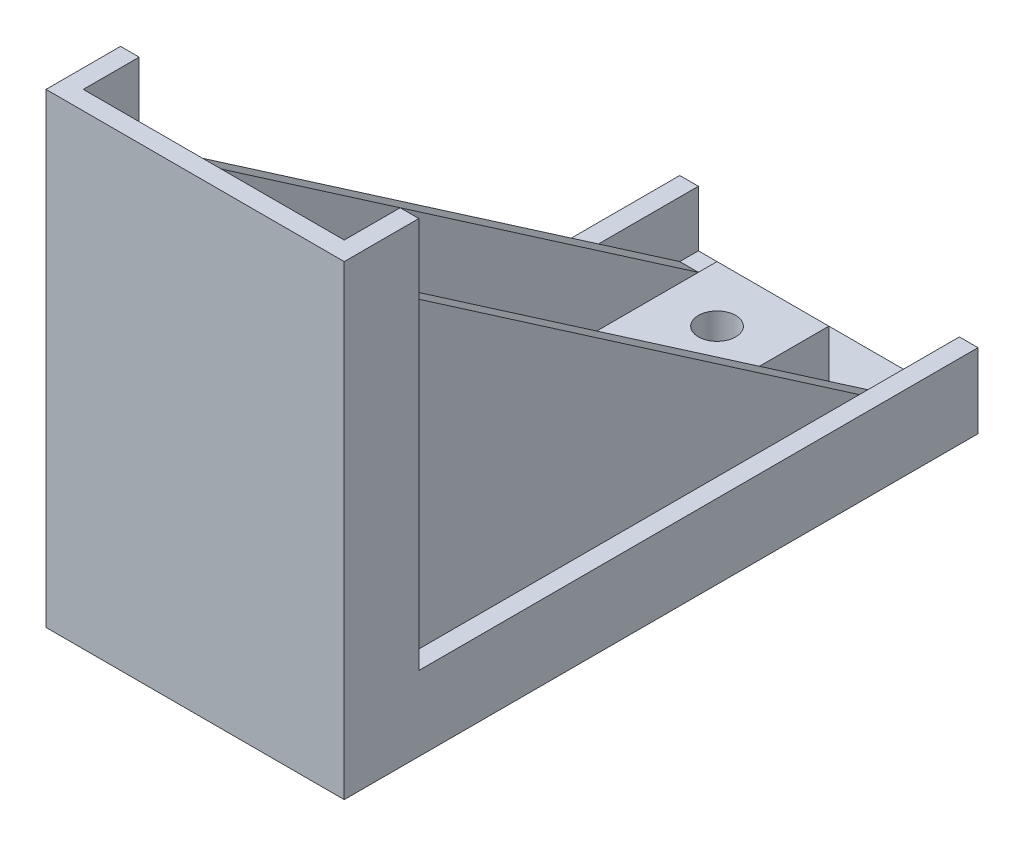
SolidWorks part; units mm, degrees
material "Plain Carbon Steel"
ref_plane "Front Plane" through (0, 0, 0) normal (0, 0, 1) x (1, 0, 0)
ref_plane "Top Plane" through (0, 0, 0) normal (0, 1, 0) x (1, 0, 0)
ref_plane "Right Plane" through (0, 0, 0) normal (1, 0, 0) x (0, 0, -1)
sketch "Sketch1" plane through (0, 0, 0) normal (0, 1, 0) x (1, 0, 0)
  line L0 (-10, 0) -> (10, 0)
  line L1 (10, 0) -> (10, 5)
  line L2 (10, 5) -> (8.75, 5)
  line L3 (8.75, 5) -> (8.75, 1.25)
  line L4 (8.75, 1.25) -> (-8.75, 1.25)
  line L5 (-8.75, 1.25) -> (-8.75, 5)
  line L6 (-8.75, 5) -> (-10, 5)
  line L7 (-10, 5) -> (-10, 0)
  dimension "D1" = 1.25
  dimension "D2" = 1.25
  dimension "D3" = 5
  dimension "D4" = 20
  dimension "D5" = 10
extrude "Boss-Extrude1" add sketch "Sketch1" along normal blind 31.25
sketch "Sketch2" plane through (0, 0, -1.25) normal (0, 0, -1) x (-1, 0, 0)
  line L0 (-10, 5) -> (-10, 0)
  line L1 (-10, 31.25) -> (-10, 0) construction
  line L2 (-10, 0) -> (10, 0)
  line L3 (10, 0) -> (10, 5)
  line L4 (10, 31.25) -> (10, 0) construction
  line L5 (10, 5) -> (8.75, 5)
  line L6 (8.75, 31.25) -> (8.75, 0) construction
  line L7 (8.75, 5) -> (8.75, 1.25)
  line L8 (8.75, 31.25) -> (8.75, 0) construction
  line L9 (8.75, 1.25) -> (-8.75, 1.25)
  line L10 (-8.75, 31.25) -> (-8.75, 0) construction
  line L11 (-8.75, 1.25) -> (-8.75, 5)
  line L12 (-8.75, 5) -> (-10, 5)
  dimension "D1" = 5
  dimension "D2" = 1.25
extrude "Boss-Extrude2" add sketch "Sketch2" along normal blind 41.25
ref_plane "Plane1" through (7.5, 0, 0) normal (1, 0, 0) x (0, 0, -1)
sketch "Sketch4" plane through (7.5, 0, 0) normal (1, 0, 0) x (0, 0, -1)
  line L0 (1.25, 28.75) -> (1.25, 1.25)
  line L2 (1.25, 1.25) -> (41.25, 1.25)
  line L4 (41.25, 1.25) -> (1.25, 28.75)
  line L5 (0, 31.25) -> (0, 0) construction
  line L6 (0, 0) -> (42.5, 0) construction
  dimension "D1" = 1.25
  dimension "D2" = 1.25
  dimension "D3" = 27.5
  dimension "D4" = 40
extrude "Boss-Extrude3" add sketch "Sketch4" along normal blind 1.25
mirror "Mirror1" about plane through (0, 0, 0) normal (1, 0, 0) of "Boss-Extrude3"
sketch "Sketch6" plane through (0, 1.25, 0) normal (0, 1, 0) x (1, 0, 0)
  line L0 (0, 0) -> (0, 42.5) construction
  line L1 (-8.75, 42.5) -> (8.75, 42.5) construction
  line L3 (3.75, 38.75) -> (-3.75, 38.75)
  line L4 (3.75, 38.75) -> (3.75, 16.25)
  line L5 (3.75, 16.25) -> (-3.75, 16.25)
  line L6 (-3.75, 38.75) -> (-3.75, 16.25)
  line L7 (3.75, 38.75) -> (-3.75, 16.25) construction
  line L8 (3.75, 16.25) -> (-3.75, 38.75) construction
  circle A0 centre (0, 35) radius 1.25
  circle A1 centre (0, 25) radius 1.25
  point P5 (0, 27.5)
  point P14 (0, 0)
  dimension "D6" = 2.5
  dimension "D1" = 7.5
  dimension "D2" = 3.75
  dimension "D3" = 22.5
  dimension "D4" = 7.5
  dimension "D5" = 10
extrude "Boss-Extrude4" add sketch "Sketch6" along normal blind 3.75
extrude "Cut-Extrude1" cut sketch "Sketch6<2>" against normal through all both and the other way through all contours A0 | A1 region at (0, 1.25, -35)
sketch "Sketch6<2>" plane through (0, 1.25, 0) normal (0, 1, 0) x (1, 0, 0) same geometry as "Sketch6"
